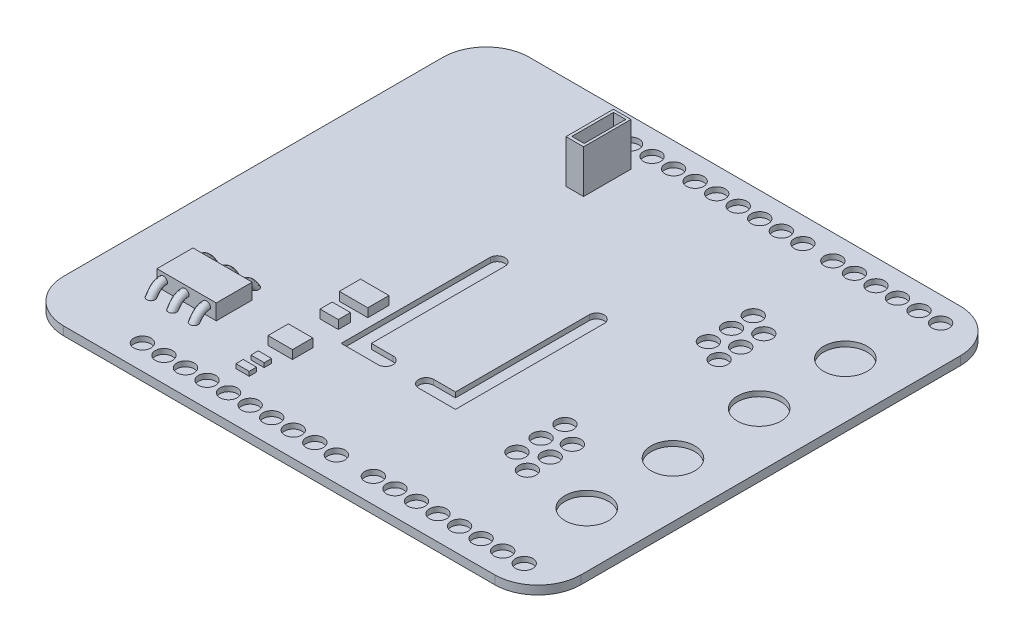
SolidWorks part; units mm, degrees
ref_plane "Plan de face" through (0, 0, 0) normal (0, 0, 1) x (1, 0, 0)
ref_plane "Plan de dessus" through (0, 0, 0) normal (0, 1, 0) x (1, 0, 0)
ref_plane "Plan de droite" through (0, 0, 0) normal (1, 0, 0) x (0, 0, -1)
sketch "Esquisse1" plane through (0, 0, 0) normal (0, 1, 0) x (1, 0, 0)
  line L1 (5, 0) -> (55, 0)
  line L2 (0, 5) -> (0, 49)
  line L3 (5, 54) -> (55, 54)
  line L4 (60, 5) -> (60, 49)
  arc A0 (55, 54) -> (60, 49) centre (55, 49) cw
  arc A1 (55, 0) -> (60, 5) centre (55, 5) ccw
  arc A2 (5, 0) -> (0, 5) centre (5, 5) cw
  arc A3 (0, 49) -> (5, 54) centre (5, 49) cw
  point P7 (60, 54)
  point P12 (0, 0)
  point P15 (0, 54)
  dimension "D3" = 5
  dimension "D1" = 54
  dimension "D2" = 60
extrude "Boss.-Extru.1" add sketch "Esquisse1" along normal blind 1
sketch "Esquisse2" plane through (0, 1, 0) normal (0, 1, 0) x (1, 0, 0)
  circle A0 centre (55.5693, 51.1519) radius 1
extrude "Enlèv. mat.-Extru.1" cut sketch "Esquisse2" against normal blind 0.6
pattern_linear "Répétition linéaire1" count 6 spacing 2.5 along (-1, 0, 0) of "Enlèv. mat.-Extru.1"
sketch "Esquisse3" plane through (0, 1, 0) normal (0, 1, 0) x (1, 0, 0)
  line L0 (50.5693, 51.1519) -> (2.7225, 51.1519) construction
  circle A0 centre (39.5923, 51.1519) radius 1
extrude "Enlèv. mat.-Extru.2" cut sketch "Esquisse3" against normal blind 0.6
pattern_linear "Répétition linéaire2" count 10 spacing 2.5 along (-1, 0, 0) of "Enlèv. mat.-Extru.2"
sketch "Esquisse4" plane through (0, 1, 0) normal (0, 1, 0) x (1, 0, 0)
  line L0 (55.5693, 51.1519) -> (55.5693, 2.85) construction
  line L1 (46.3467, 0) -> (65.7685, 0) construction
  line L2 (5, 0) -> (55, 0) construction
  circle A0 centre (55.5693, 2.85) radius 1
  dimension "D1" = 2.85
extrude "Enlèv. mat.-Extru.3" cut sketch "Esquisse4" against normal blind 0.6
pattern_linear "Répétition linéaire3" count 8 spacing 2.5 along (-1, 0, 0) of "Enlèv. mat.-Extru.3"
sketch "Esquisse5" plane through (0, 1, 0) normal (0, 1, 0) x (1, 0, 0)
  line L0 (55.5693, 2.85) -> (2.705, 2.85) construction
  circle A0 centre (33.7737, 2.85) radius 1
extrude "Enlèv. mat.-Extru.4" cut sketch "Esquisse5" against normal blind 0.6
pattern_linear "Répétition linéaire4" count 10 spacing 2.5 along (-1, 0, 0) of "Enlèv. mat.-Extru.4"
sketch "Esquisse6" plane through (0, 1, 0) normal (0, 1, 0) x (1, 0, 0)
  circle A0 centre (53.6323, 42.0419) radius 2.5284
extrude "Enlèv. mat.-Extru.5" cut sketch "Esquisse6" against normal blind 0.6
pattern_linear "Répétition linéaire5" count 4 spacing 10 along (0, 0, 1) of "Enlèv. mat.-Extru.5"
sketch "Esquisse7" plane through (0, 1, 0) normal (0, 1, 0) x (1, 0, 0)
  line L0 (46.3863, 39.824) -> (46.3863, 8.106) construction
  line L1 (43.9644, 41.0268) -> (43.9644, 6.4646) construction
  circle A0 centre (46.3863, 34.6371) radius 1
  circle A1 centre (46.3863, 37.1476) radius 1
  circle A2 centre (46.3863, 39.824) radius 1
  circle A3 centre (43.9644, 35.8169) radius 1
  circle A4 centre (43.9644, 38.4998) radius 1
  circle A5 centre (43.9644, 41.0268) radius 1
  circle A6 centre (46.3863, 12.4023) radius 1
  circle A7 centre (46.3863, 15.0487) radius 1
  circle A8 centre (46.3863, 17.6149) radius 1
  circle A9 centre (43.9644, 13.6052) radius 1
  circle A10 centre (43.9644, 16.412) radius 1
  circle A11 centre (43.9644, 19.1787) radius 1
extrude "Enlèv. mat.-Extru.6" cut sketch "Esquisse7" against normal blind 0.6
sketch "Esquisse8" plane through (0, 1, 0) normal (0, 1, 0) x (1, 0, 0)
  line L0 (31.8233, 14.3423) -> (36.1009, 14.3423)
  line L1 (36.1009, 14.3423) -> (36.1009, 31.6633)
  line L2 (31.8233, 16.0955) -> (34.3478, 16.0955)
  line L3 (34.3478, 16.0955) -> (34.3478, 31.6633)
  arc A0 (31.8233, 14.3423) -> (31.8233, 16.0955) centre (31.8233, 15.2189) cw
  arc A1 (34.3478, 31.5064) -> (36.1009, 31.6633) centre (35.2244, 31.5849) cw
extrude "Enlèv. mat.-Extru.7" cut sketch "Esquisse8" against normal blind 0.6 contours A1 L3 L2 A0 L0 L1 | A1 L1 L0 A0 L2 L3 region at (34.8462, 1, -22.0821)
sketch "Esquisse9" plane through (0, 1, 0) normal (0, 1, 0) x (1, 0, 0)
  line L0 (29.4689, 11.8287) -> (29.4689, 55.7003) construction
ref_plane "Plan1" through (29.4689, 0, 0) normal (1, 0, 0) x (0, 0, -1)
mirror "Symétrie1" about plane through (29.4689, 0, 0) normal (1, 0, 0) of "Enlèv. mat.-Extru.7"
sketch "Esquisse13" plane through (0, 1, 0) normal (0, 1, 0) x (1, 0, 0)
  line L1 (20.1083, 48.654) -> (22.149, 48.654)
  line L2 (20.1083, 48.654) -> (20.1083, 43.1536)
  line L3 (20.1083, 43.1536) -> (22.149, 43.1536)
  line L4 (22.149, 48.654) -> (22.149, 43.1536)
extrude "Boss.-Extru.3" add sketch "Esquisse13" along normal blind 5
sketch "Esquisse14" plane through (0, 6, 0) normal (0, 1, 0) x (1, 0, 0)
  line L1 (21.8507, 48.3487) -> (20.4262, 48.3487)
  line L2 (21.8507, 48.3487) -> (21.8507, 43.5204)
  line L3 (21.8507, 43.5204) -> (20.4262, 43.5204)
  line L4 (20.4262, 48.3487) -> (20.4262, 43.5204)
extrude "Enlèv. mat.-Extru.9" cut sketch "Esquisse14" against normal blind 3
sketch "Esquisse15" plane through (0, 1, 0) normal (0, 1, 0) x (1, 0, 0)
  line L1 (13.3286, 9.3622) -> (6.4512, 9.3622)
  line L2 (13.3286, 9.3622) -> (13.3286, 13.5364)
  line L3 (13.3286, 13.5364) -> (6.4512, 13.5364)
  line L4 (6.4512, 9.3622) -> (6.4512, 13.5364)
extrude "Boss.-Extru.4" add sketch "Esquisse15" along normal blind 1.8
sketch "Esquisse16" plane through (0, 1, 0) normal (0, 1, 0) x (1, 0, 0)
  line L0 (7.1871, 7.9375) -> (7.1871, -12.7625) construction
  circle A0 centre (7.1871, 7.9375) radius 0.4836
ref_plane "Plan2" through (7.1871, 0, 0) normal (-1, 0, 0) x (0, 0, 1)
sketch "Esquisse17" plane through (7.1871, 0, 0) normal (-1, 0, 0) x (0, 0, 1)
  spline S0 degree 2 poles (-7.9375, 1) (-8.6966, 2.259) (-9.7079, 1.9415) knots 0 0 0 1 1 1
sweep "Balayage1" add profiles "Esquisse16" path "Esquisse17"
ref_plane "Plan3" through (0, 0, -11.4493) normal (0, 0, -1) x (-1, 0, 0)
mirror "Symétrie2" about plane through (0, 0, -11.4493) normal (0, 0, -1) of "Balayage1"
pattern_linear "Répétition linéaire6" count 3 spacing 2.5 along (1, 0, 0) of "Symétrie2"
sketch "Esquisse18" plane through (0, 1, 0) normal (0, 1, 0) x (1, 0, 0)
  line L1 (19.2751, 5.6997) -> (20.8129, 5.6997)
  line L2 (19.2751, 5.6997) -> (19.2751, 6.5497)
  line L3 (19.2751, 6.5497) -> (20.8129, 6.5497)
  line L4 (20.8129, 5.6997) -> (20.8129, 6.5497)
  line L5 (19.2751, 7.4425) -> (20.8129, 7.4425)
  line L6 (19.2751, 7.4425) -> (19.2751, 8.29)
  line L7 (19.2751, 8.29) -> (20.8129, 8.29)
  line L8 (20.8129, 7.4425) -> (20.8129, 8.29)
  dimension "D1" = 0.8475
  dimension "D2" = 0.85
extrude "Boss.-Extru.5" add sketch "Esquisse18" along normal blind 0.5
sketch "Esquisse19" plane through (0, 1, 0) normal (0, 1, 0) x (1, 0, 0)
  line L1 (21.6389, 9.891) -> (18.8118, 9.891)
  line L2 (21.6389, 9.891) -> (21.6389, 12.2477)
  line L3 (21.6389, 12.2477) -> (18.8118, 12.2477)
  line L4 (18.8118, 9.891) -> (18.8118, 12.2477)
extrude "Boss.-Extru.6" add sketch "Esquisse19" along normal blind 1
sketch "Esquisse20" plane through (0, 1, 0) normal (0, 1, 0) x (1, 0, 0)
  line L1 (21.278, 15.5696) -> (19.1647, 15.5696)
  line L2 (21.278, 15.5696) -> (21.278, 16.9798)
  line L3 (21.278, 16.9798) -> (19.1647, 16.9798)
  line L4 (19.1647, 15.5696) -> (19.1647, 16.9798)
  line L5 (21.8032, 18.464) -> (18.5035, 18.464)
  line L6 (21.8032, 18.464) -> (21.8032, 20.9251)
  line L7 (21.8032, 20.9251) -> (18.5035, 20.9251)
  line L8 (18.5035, 18.464) -> (18.5035, 20.9251)
extrude "Boss.-Extru.7" add sketch "Esquisse20" along normal blind 1
